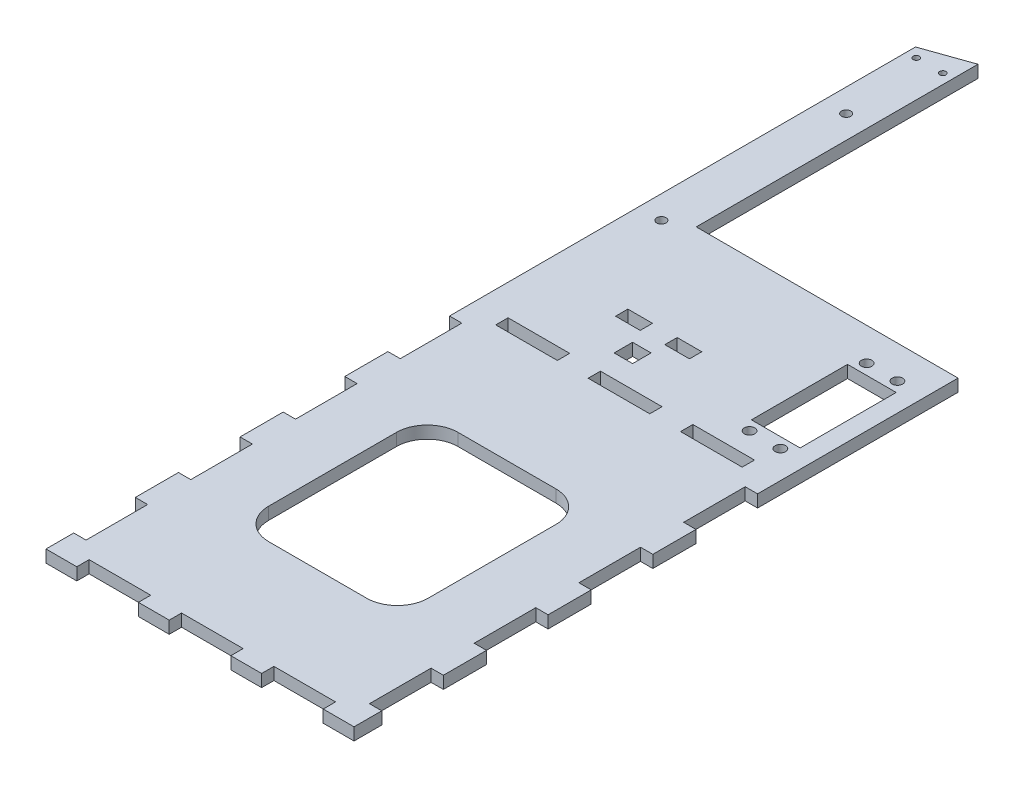
SolidWorks part; units mm, degrees
ref_plane "Front Plane" through (0, 0, 0) normal (0, 0, 1) x (1, 0, 0)
ref_plane "Top Plane" through (0, 0, 0) normal (0, 1, 0) x (1, 0, 0)
ref_plane "Right Plane" through (0, 0, 0) normal (1, 0, 0) x (0, 0, -1)
sketch "Sketch2" plane through (0, 0, 0) normal (0, 1, 0) x (1, 0, 0)
  line L0 (-19.05, -71.2393) -> (-19.05, -249.0393)
  line L1 (0, 0) -> (107.95, 0)
  line L2 (-19.05, -249.0393) -> (107.95, -249.0393)
  line L3 (107.95, -249.0393) -> (107.95, -60.96)
  line L4 (107.95, 0) -> (107.95, -60.96)
  line L5 (-19.05, -71.2393) -> (-19.05, 109.4501)
  line L6 (-19.05, 109.4501) -> (0, 116.1658)
  line L7 (0, 116.1658) -> (0, 97.4731)
  line L8 (0, 65.786) -> (0, 0)
  line L9 (0, 65.786) -> (0, 97.4731)
  dimension "D1" = 107.95
  dimension "D2" = 60.96
  dimension "D3" = 180.6894
  dimension "D4" = 180
  dimension "D5" = 127
  dimension "D7" = 90
  dimension "D8" = 90
  dimension "D9" = 177.8
extrude "Boss-Extrude1" add sketch "Sketch2" along normal blind 5.08
sketch "Sketch3" plane through (0, 5.08, 0) normal (0, 1, 0) x (1, 0, 0)
  line L0 (-19.05, -249.0393) -> (107.95, -249.0393) construction
  line L1 (80.264, -17.8917) -> (100.33, -17.8917)
  line L2 (80.264, -17.8917) -> (80.264, -57.5157)
  line L3 (80.264, -57.5157) -> (100.33, -57.5157)
  line L4 (100.33, -17.8917) -> (100.33, -57.5157)
  line L7 (107.95, -249.0393) -> (107.95, 0) construction
  dimension "D1" = 20.066
  dimension "D2" = 39.624
  dimension "D3" = 191.5236
  dimension "D4" = 7.62
extrude "Cut-Extrude1" cut sketch "Sketch3" against normal up to surface (5.08 mm away) up to face at (29.6333, 0, 45.4105)
sketch "Sketch4" plane through (0, 5.08, 0) normal (0, 1, 0) x (1, 0, 0)
  line L0 (80.264, -17.8917) -> (80.264, -57.5157) construction
  line L1 (100.33, -57.5157) -> (100.33, -17.8917) construction
  line L2 (100.33, -17.8917) -> (80.264, -17.8917) construction
  line L3 (80.264, -57.5157) -> (100.33, -57.5157) construction
  circle A0 centre (83.82, -13.5737) radius 2.159
  circle A1 centre (96.52, -13.5737) radius 2.159
  circle A2 centre (83.82, -61.8337) radius 2.159
  circle A3 centre (96.52, -61.8337) radius 2.159
  dimension "D1" = 4.318
  dimension "D3" = 3.556
  dimension "D6" = 12.7
  dimension "D7" = 3.81
  dimension "D2" = 12.7
  dimension "D4" = 3.81
  dimension "D5" = 4.318
  dimension "D8" = 4.318
  dimension "D9" = 4.318
extrude "Cut-Extrude2" cut sketch "Sketch4" against normal up to surface (5.08 mm away) up to face at (90.297, 0, 37.7037)
sketch "Sketch5" plane through (0, 5.08, 0) normal (0, 1, 0) x (1, 0, 0)
  line L0 (-19.05, 109.4501) -> (-19.05, -249.0393) construction
  line L1 (24.257, -122.4614) -> (64.6111, -122.4614)
  line L2 (11.557, -135.1614) -> (11.557, -187.8191)
  line L3 (24.257, -200.5191) -> (64.6111, -200.5191)
  line L4 (77.3111, -135.1614) -> (77.3111, -187.8191)
  line L5 (107.95, -249.0393) -> (107.95, 0) construction
  line L6 (107.95, 0) -> (0, 0) construction
  line L7 (-19.05, -249.0393) -> (107.95, -249.0393) construction
  arc A0 (77.3111, -135.1614) -> (64.6111, -122.4614) centre (64.6111, -135.1614) ccw
  arc A1 (64.6111, -200.5191) -> (77.3111, -187.8191) centre (64.6111, -187.8191) ccw
  arc A2 (11.557, -187.8191) -> (24.257, -200.5191) centre (24.257, -187.8191) ccw
  arc A3 (11.557, -135.1614) -> (24.257, -122.4614) centre (24.257, -135.1614) cw
  dimension "D2" = 12.7
  dimension "D1" = 30.607
  dimension "D3" = 30.6389
  dimension "D4" = 122.4614
  dimension "D5" = 48.5203
extrude "Cut-Extrude3" cut sketch "Sketch5" against normal up to surface (5.08 mm away) up to face at (96.52, 0, 63.9927)
sketch "Sketch6" plane through (0, 5.08, 0) normal (0, 1, 0) x (1, 0, 0)
  line L0 (107.95, -249.0393) -> (107.95, 0) construction
  line L1 (102.87, -237.6093) -> (107.95, -237.6093)
  line L2 (102.87, -237.6093) -> (102.87, -212.2093)
  line L3 (102.87, -212.2093) -> (107.95, -212.2093)
  line L4 (107.95, -237.6093) -> (107.95, -212.2093)
  line L5 (-19.05, -249.0393) -> (107.95, -249.0393) construction
  dimension "D1" = 5.08
  dimension "D2" = 11.43
  dimension "D3" = 25.4
extrude "Cut-Extrude4" cut sketch "Sketch6" against normal up to surface (5.08 mm away) up to face at (44.4341, 0, 161.4902)
sketch "Sketch7" plane through (0, 5.08, 0) normal (0, 1, 0) x (1, 0, 0)
  line L0 (107.95, -212.2093) -> (107.95, 0) construction
  line L1 (102.87, -194.4293) -> (107.95, -194.4293)
  line L2 (102.87, -194.4293) -> (102.87, -169.0293)
  line L3 (102.87, -169.0293) -> (107.95, -169.0293)
  line L4 (107.95, -194.4293) -> (107.95, -169.0293)
  line L5 (107.95, -212.2093) -> (102.87, -212.2093) construction
  dimension "D1" = 5.08
  dimension "D2" = 25.4
  dimension "D3" = 17.78
extrude "Cut-Extrude5" cut sketch "Sketch7" against normal up to surface (5.08 mm away) up to face at (44.4341, 0, 161.4902)
sketch "Sketch8" plane through (0, 5.08, 0) normal (0, 1, 0) x (1, 0, 0)
  line L0 (107.95, -169.0293) -> (107.95, 0) construction
  line L1 (102.87, -151.2493) -> (107.95, -151.2493)
  line L2 (102.87, -151.2493) -> (102.87, -125.8493)
  line L3 (102.87, -125.8493) -> (107.95, -125.8493)
  line L4 (107.95, -151.2493) -> (107.95, -125.8493)
  line L5 (102.87, -108.0693) -> (107.95, -108.0693)
  line L6 (102.87, -108.0693) -> (102.87, -82.6693)
  line L7 (102.87, -82.6693) -> (107.95, -82.6693)
  line L8 (107.95, -108.0693) -> (107.95, -82.6693)
  line L9 (107.95, -169.0293) -> (102.87, -169.0293) construction
  dimension "D1" = 5.08
  dimension "D2" = 17.78
  dimension "D3" = 5.08
  dimension "D4" = 25.4
  dimension "D5" = 17.78
  dimension "D6" = 25.4
extrude "Cut-Extrude6" cut sketch "Sketch8" against normal up to surface (5.08 mm away) up to face at (44.4341, 0, 161.4902)
sketch "Sketch9" plane through (0, 5.08, 0) normal (0, 1, 0) x (1, 0, 0)
  line L0 (-19.05, 109.4501) -> (-19.05, -249.0393) construction
  line L1 (-19.05, -237.6093) -> (-13.97, -237.6093)
  line L2 (-19.05, -237.6093) -> (-19.05, -212.2093)
  line L3 (-19.05, -212.2093) -> (-13.97, -212.2093)
  line L4 (-13.97, -237.6093) -> (-13.97, -212.2093)
  line L5 (-19.05, -194.4293) -> (-13.97, -194.4293)
  line L6 (-19.05, -194.4293) -> (-19.05, -169.0293)
  line L7 (-19.05, -169.0293) -> (-13.97, -169.0293)
  line L8 (-13.97, -194.4293) -> (-13.97, -169.0293)
  line L9 (-19.05, -151.2493) -> (-13.97, -151.2493)
  line L10 (-19.05, -151.2493) -> (-19.05, -125.8493)
  line L11 (-19.05, -125.8493) -> (-13.97, -125.8493)
  line L12 (-13.97, -151.2493) -> (-13.97, -125.8493)
  line L13 (-19.05, -108.0693) -> (-13.97, -108.0693)
  line L14 (-19.05, -108.0693) -> (-19.05, -82.6693)
  line L15 (-19.05, -82.6693) -> (-13.97, -82.6693)
  line L16 (-13.97, -108.0693) -> (-13.97, -82.6693)
  line L17 (102.87, -237.6093) -> (107.95, -237.6093) construction
  line L18 (107.95, -212.2093) -> (102.87, -212.2093) construction
  line L19 (102.87, -194.4293) -> (107.95, -194.4293) construction
  line L20 (107.95, -169.0293) -> (102.87, -169.0293) construction
  line L21 (102.87, -151.2493) -> (107.95, -151.2493) construction
  line L22 (107.95, -125.8493) -> (102.87, -125.8493) construction
  line L23 (102.87, -108.0693) -> (107.95, -108.0693) construction
  line L24 (107.95, -82.6693) -> (102.87, -82.6693) construction
  dimension "D1" = 5.08
  dimension "D2" = 5.08
  dimension "D3" = 5.08
  dimension "D4" = 5.08
  dimension "D5" = 0
  dimension "D6" = 0
  dimension "D7" = 0
  dimension "D8" = 0
  dimension "D9" = 0
  dimension "D10" = 0
  dimension "D11" = 0
  dimension "D12" = 0
extrude "Cut-Extrude7" cut sketch "Sketch9" against normal up to surface (5.08 mm away) up to face at (44.4341, 0, 161.4902)
sketch "Sketch10" plane through (0, 5.08, 0) normal (0, 1, 0) x (1, 0, 0)
  line L0 (-19.05, 109.4501) -> (-19.05, -82.6693) construction
  line L1 (-6.35, -71.2393) -> (19.05, -71.2393)
  line L2 (-6.35, -71.2393) -> (-6.35, -76.3193)
  line L3 (-6.35, -76.3193) -> (19.05, -76.3193)
  line L4 (19.05, -71.2393) -> (19.05, -76.3193)
  line L5 (-13.97, -82.6693) -> (-19.05, -82.6693) construction
  line L8 (31.75, -71.2393) -> (57.15, -71.2393)
  line L9 (31.75, -71.2393) -> (31.75, -76.3193)
  line L10 (31.75, -76.3193) -> (57.15, -76.3193)
  line L11 (57.15, -71.2393) -> (57.15, -76.3193)
  line L12 (69.85, -71.2393) -> (95.25, -71.2393)
  line L13 (69.85, -71.2393) -> (69.85, -76.3193)
  line L14 (69.85, -76.3193) -> (95.25, -76.3193)
  line L15 (95.25, -71.2393) -> (95.25, -76.3193)
  dimension "D1" = 5.08
  dimension "D2" = 12.7
  dimension "D3" = 6.35
  dimension "D4" = 25.4
  dimension "D5" = 25.4
  dimension "D6" = 12.7
  dimension "D7" = 0
  dimension "D8" = 5.08
  dimension "D9" = 5.08
  dimension "D10" = 0
  dimension "D11" = 25.4
  dimension "D12" = 12.7
extrude "Cut-Extrude8" cut sketch "Sketch10" against normal up to surface (5.08 mm away) up to face at (44.4341, 0, 161.4902)
sketch "Sketch11" plane through (0, 5.08, 0) normal (0, 1, 0) x (1, 0, 0)
  line L0 (-19.05, -249.0393) -> (107.95, -249.0393) construction
  line L1 (-6.35, -243.9593) -> (19.05, -243.9593)
  line L2 (-6.35, -243.9593) -> (-6.35, -249.0393)
  line L3 (-6.35, -249.0393) -> (19.05, -249.0393)
  line L4 (19.05, -243.9593) -> (19.05, -249.0393)
  line L5 (-6.35, -71.2393) -> (-6.35, -76.3193) construction
  line L6 (19.05, -76.3193) -> (19.05, -71.2393) construction
  line L7 (31.75, -71.2393) -> (31.75, -76.3193) construction
  line L8 (31.75, -243.9593) -> (57.15, -243.9593)
  line L9 (31.75, -243.9593) -> (31.75, -249.0393)
  line L10 (31.75, -249.0393) -> (57.15, -249.0393)
  line L11 (57.15, -243.9593) -> (57.15, -249.0393)
  line L12 (69.85, -243.9593) -> (95.25, -243.9593)
  line L13 (69.85, -243.9593) -> (69.85, -249.0393)
  line L14 (69.85, -249.0393) -> (95.25, -249.0393)
  line L15 (95.25, -243.9593) -> (95.25, -249.0393)
  line L16 (57.15, -76.3193) -> (57.15, -71.2393) construction
  line L17 (69.85, -71.2393) -> (69.85, -76.3193) construction
  line L18 (95.25, -76.3193) -> (95.25, -71.2393) construction
  dimension "D1" = 5.08
  dimension "D2" = 0
  dimension "D3" = 0
  dimension "D4" = 5.08
  dimension "D5" = 5.08
  dimension "D6" = 0
  dimension "D7" = 0
  dimension "D8" = 0
  dimension "D9" = 0
extrude "Cut-Extrude9" cut sketch "Sketch11" against normal up to surface (5.08 mm away) up to face at (82.55, 0, 73.7793)
sketch "Sketch12" plane through (0, 5.08, 0) normal (0, 1, 0) x (1, 0, 0)
  line L0 (-19.05, 109.4501) -> (-19.05, -82.6693) construction
  line L1 (0, 0) -> (0, 116.1658) construction
  circle A0 centre (-14.998, 105.7009) radius 1.27
  circle A1 centre (-4.064, 105.7009) radius 1.27
  dimension "D1" = 2.54
  dimension "D3" = 4.064
  dimension "D2" = 4.052
extrude "Cut-Extrude10" cut sketch "Sketch12" against normal up to surface (5.08 mm away) up to face at (82.55, 0, 73.7793)
sketch "Sketch13" plane through (0, 5.08, 0) normal (0, 1, 0) x (1, 0, 0)
  line L0 (-19.05, 109.4501) -> (-19.05, -82.6693) construction
  line L1 (15.24, -43.4347) -> (25.4, -43.4347)
  line L2 (15.24, -43.4347) -> (15.24, -48.5147)
  line L3 (15.24, -48.5147) -> (25.4, -48.5147)
  line L4 (25.4, -43.4347) -> (25.4, -48.5147)
  line L5 (35.56, -43.4347) -> (45.72, -43.4347)
  line L6 (35.56, -43.4347) -> (35.56, -48.5147)
  line L7 (35.56, -48.5147) -> (45.72, -48.5147)
  line L8 (45.72, -43.4347) -> (45.72, -48.5147)
  line L10 (80.264, -57.5157) -> (80.264, -17.8917) construction
  dimension "D1" = 5.08
  dimension "D2" = 5.08
  dimension "D3" = 10.16
  dimension "D4" = 10.16
  dimension "D5" = 10.16
  dimension "D6" = 34.29
  dimension "D7" = 34.544
extrude "Cut-Extrude11" cut sketch "Sketch13" against normal up to surface (5.08 mm away) up to face at (-4.064, 0, -104.4309)
sketch "Sketch14" plane through (0, 5.08, 0) normal (0, 1, 0) x (1, 0, 0)
  line L0 (35.56, -48.5147) -> (45.72, -48.5147) construction
  line L1 (28.067, -54.3098) -> (35.687, -54.3098)
  line L2 (28.067, -54.3098) -> (28.067, -61.9298)
  line L3 (28.067, -61.9298) -> (35.687, -61.9298)
  line L4 (35.687, -54.3098) -> (35.687, -61.9298)
  line L6 (-19.05, 109.4501) -> (-19.05, -82.6693) construction
  dimension "D1" = 5.7951
  dimension "D2" = 7.62
  dimension "D3" = 7.62
  dimension "D4" = 47.117
extrude "Cut-Extrude12" cut sketch "Sketch14" against normal up to surface (5.08 mm away) up to face at (40.64, 0, 45.9747)
sketch "Sketch15" plane through (0, 5.08, 0) normal (0, 1, 0) x (1, 0, 0)
  line L1 (0, 0) -> (0, 116.1658) construction
  line L2 (-19.05, 109.4501) -> (-19.05, -82.6693) construction
  circle A0 centre (-9.5377, 71.3501) radius 1.905
  circle A1 centre (-9.5377, -4.8499) radius 1.905
  dimension "D1" = 3.81
  dimension "D2" = 76.2
  dimension "D3" = 38.1
  dimension "D4" = 9.5377
  dimension "D5" = 9.5123
extrude "Cut-Extrude13" cut sketch "Sketch15" against normal up to surface (5.08 mm away) up to face at (31.877, 0, 58.1198)
